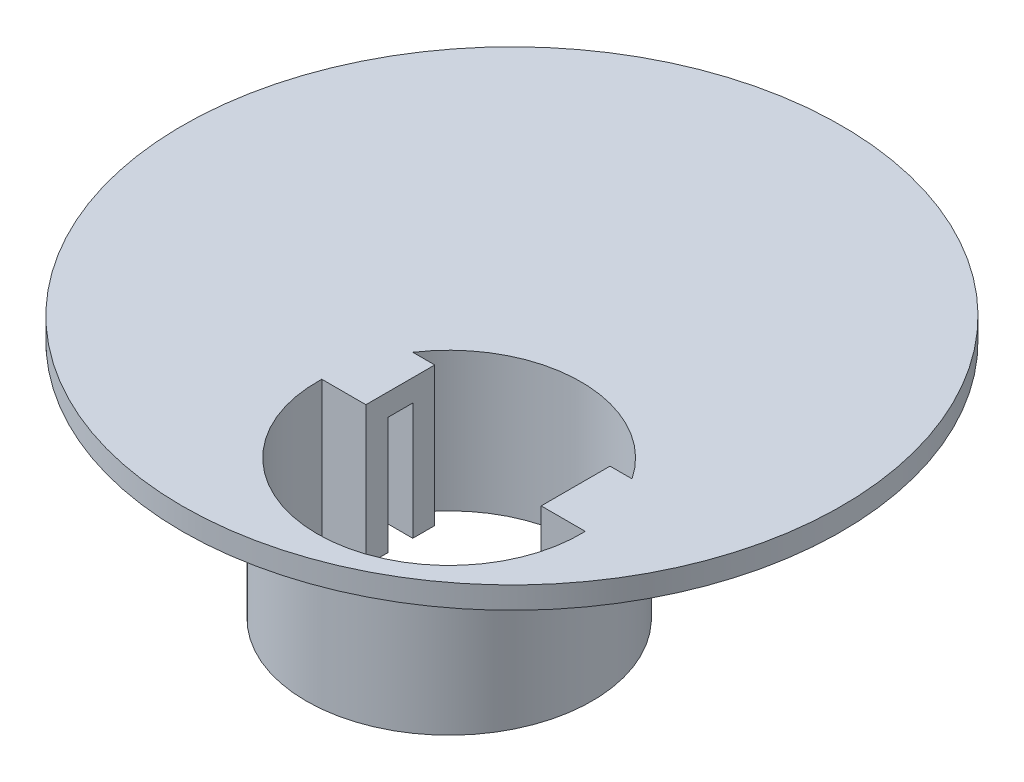
SolidWorks part; units mm, degrees
ref_plane "Front Plane" through (0, 0, 0) normal (0, 0, 1) x (1, 0, 0)
ref_plane "Top Plane" through (0, 0, 0) normal (0, 1, 0) x (1, 0, 0)
ref_plane "Right Plane" through (0, 0, 0) normal (1, 0, 0) x (0, 0, -1)
sketch "Sketch1" plane through (0, 0, 0) normal (0, 1, 0) x (1, 0, 0)
  line L0 (-2.5682, -8.7367) -> (0.2667, -8.7367)
  line L1 (6.25, -19.5367) -> (6.25, -17.8592)
  line L2 (-2.0416, -7.0367) -> (0.2667, -7.0367)
  line L3 (-1.2333, -5.5367) -> (0.2667, -5.5367)
  line L4 (0.2667, -5.5367) -> (0.2667, -7.0367)
  line L5 (0.2667, -8.7367) -> (0.2667, -10.2367)
  line L6 (0.2667, -10.2367) -> (-2.745, -10.2367)
  line L7 (12.2333, -5.5367) -> (12.2333, -7.0367)
  line L8 (13.7333, -5.5367) -> (12.2333, -5.5367)
  line L9 (14.5416, -7.0367) -> (12.2333, -7.0367)
  line L10 (15.0682, -8.7367) -> (12.2333, -8.7367)
  line L11 (12.2333, -8.7367) -> (12.2333, -10.2367)
  line L12 (12.2333, -10.2367) -> (15.245, -10.2367)
  line L13 (0.2667, -7.0367) -> (0.2667, -8.7367)
  line L14 (12.2333, -7.0367) -> (12.2333, -8.7367)
  circle A0 centre (-13.75, 8.9633) radius 2.55
  circle A1 centre (6.25, -10.5367) radius 9.7618
  circle A2 centre (6.25, -10.5367) radius 9
  point P7 (-0.8874, -7.0367)
  point P20 (13.3874, -7.0367)
  circle B0 centre (0, 0) radius 22.5
  circle B1 centre (6.25, -10.5367) radius 10
  circle B2 centre (-13.75, 8.9633) radius 4.75
  dimension "D1" = 5.1
  dimension "D2" = 18
  dimension "D3" = 10.8
  dimension "D4" = 1.7
  dimension "D5" = 1.5
  dimension "D6" = 1.5
  dimension "D7" = 1.5
sketch_block_instance "Block1-1"
sketch_block "Block1" parameters "D1"=45
extrude "Boss-Extrude1" add sketch "Sketch1" along normal blind 1.5 contours B0 B2 B1 | B2 A0 | A0 | A1 A2 | B1 A1 | L3 A2 L2 L4 | L2 A2 L0 L13 | L0 A2 L6 L5 | L9 A2 L8 L7 | L10 A2 L9 L14 | L12 A2 L10 L11 region at (-1.0389, 0, 7.9153) region at (-1.2061, 0, 9.4942) region at (-0.7147, 0, 6.3388) region at (13.2147, 0, 6.3388) region at (13.5389, 0, 7.9153) region at (13.7061, 0, 9.4942) region at (-13.75, 0, -8.9633) region at (-3.2357, 0, 10.5367) region at (-0.8204, 0, -2.2191) region at (-3.7217, 0, 10.5367) region at (-18.3656, 0, -8.9633)
extrude "Boss-Extrude2" add sketch "Sketch1<3>" against normal blind 8 contours A1 A2 | A0 | L9 A2 L8 L7 | L12 A2 L10 L11 | L0 A2 L6 L5 | L3 A2 L2 L4 region at (-1.2061, 0, 9.4942) region at (-0.7147, 0, 6.3388) region at (13.2147, 0, 6.3388) region at (13.7061, 0, 9.4942) region at (-13.75, 0, -8.9633) region at (-3.2357, 0, 10.5367)
sketch "Sketch1<3>" plane through (0, 0, 0) normal (0, 1, 0) x (1, 0, 0) same geometry as "Sketch1"
fillet "Fillet1" radius 1 1 edges at (-13.75, -8, -6.4133)
sketch "Sketch2"
sketch_block_instance "Block3-1"
sketch_block "Block3"
sketch_block_instance "Block2-1"
sketch_block "Block2" parameters "D1"=27.3, "D2"=27.3
